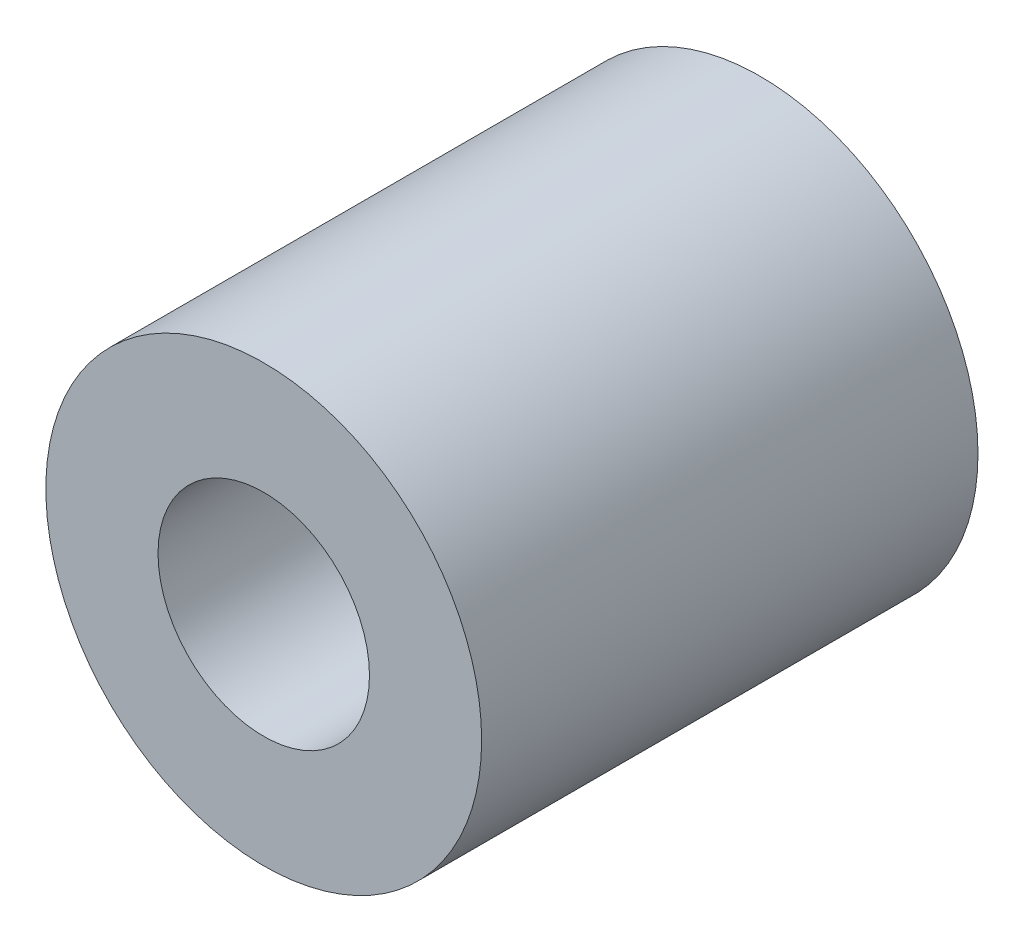
SolidWorks part; units mm, degrees
ref_plane "Front Plane" through (0, 0, 0) normal (0, 0, 1) x (1, 0, 0)
ref_plane "Top Plane" through (0, 0, 0) normal (0, 1, 0) x (1, 0, 0)
ref_plane "Right Plane" through (0, 0, 0) normal (1, 0, 0) x (0, 0, -1)
sketch "Sketch1" plane through (0, 0, 0) normal (0, 0, 1) x (1, 0, 0)
  circle A0 centre (0, 0) radius 2.7877
  dimension "D1" = 5.5753
extrude "Boss-Extrude1" add sketch "Sketch1" along normal blind 6.35
hole_wizard "#6-32 Tapped Hole1" positions "Sketch2" profile "Sketch4" tap size "#6-32" standard "ANSI Inch"
sketch "Sketch2" plane through (0, 0, 0) normal (0, 0, -1) x (-1, 0, 0)
  point P0 (0, 0)
sketch "Sketch4" plane through (0, 0, 0) normal (1, 0, 0) x (0, 1, 0)
  line L0 (0, 0) -> (0, 10.2107)
  line L1 (0, 10.2107) -> (1.3525, 9.398)
  line L2 (1.3525, 9.398) -> (1.3525, 0)
  line L5 (1.3525, 0) -> (0, 0)
  line L10 (0, 10.2107) -> (-1.3526, 9.398) construction
  line L11 (0, -6.35) -> (0, 107.95) construction
  dimension "Tap Drill Dia." = 2.7051
  dimension "Tap Drill Depth" = 9.398
  dimension "Drill Angle" = 118
cosmetic thread "Hole Thread1" parameters "D1"=7.0104, "D2"=3.5052
ref_axis "Axis1" through (0, 0, -0.3175) along (0, 0, 1)
